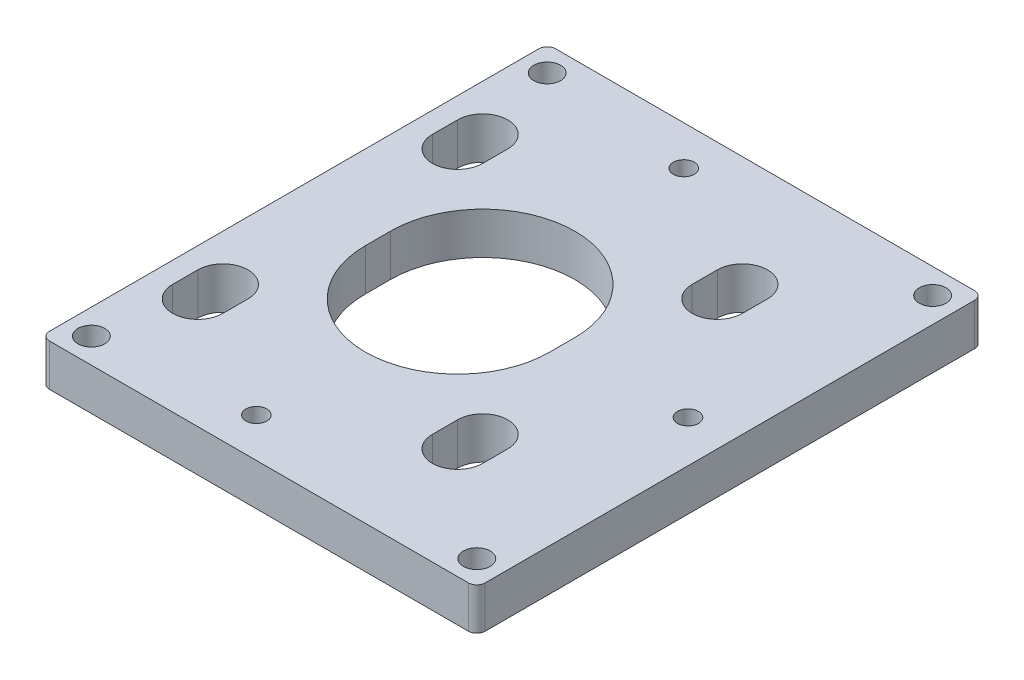
SolidWorks part; units mm, degrees
material "AISI 1045 Steel, cold drawn"
ref_plane "Front Plane" through (0, 0, 0) normal (0, 0, 1) x (1, 0, 0)
ref_plane "Top Plane" through (0, 0, 0) normal (0, 1, 0) x (1, 0, 0)
ref_plane "Right Plane" through (0, 0, 0) normal (1, 0, 0) x (0, 0, -1)
sketch "Sketch1" plane through (0, 0, 0) normal (0, 1, 0) x (1, 0, 0)
  line L0 (0, -1.5) -> (0, 1.5) construction
  line L1 (-11, -1.5) -> (-11, 1.5)
  line L2 (11, -1.5) -> (11, 1.5)
  line L3 (-15.5, 14) -> (-15.5, 17) construction
  line L4 (-18.5, 14) -> (-18.5, 17)
  line L5 (-12.5, 14) -> (-12.5, 17)
  line L6 (15.5, 14) -> (15.5, 17) construction
  line L7 (12.5, 14) -> (12.5, 17)
  line L8 (18.5, 14) -> (18.5, 17)
  line L9 (15.5, -17) -> (15.5, -14) construction
  line L10 (12.5, -17) -> (12.5, -14)
  line L11 (18.5, -17) -> (18.5, -14)
  line L12 (-15.5, -17) -> (-15.5, -14) construction
  line L13 (-18.5, -17) -> (-18.5, -14)
  line L14 (-12.5, -17) -> (-12.5, -14)
  line L15 (-15.5, 15.5) -> (15.5, 15.5) construction
  line L16 (-15.5, -15.5) -> (-15.5, 15.5) construction
  line L17 (21, -30.2) -> (21, 30.2) construction
  line L18 (-21, 30.2) -> (31, 30.2)
  line L19 (-21, 30.2) -> (-21, -30.2)
  line L20 (-21, -30.2) -> (31, -30.2)
  line L21 (31, 30.2) -> (31, -30.2)
  arc A0 (-11, -1.5) -> (11, -1.5) centre (0, -1.5) ccw
  arc A1 (11, 1.5) -> (-11, 1.5) centre (0, 1.5) ccw
  arc A2 (-18.5, 14) -> (-12.5, 14) centre (-15.5, 14) ccw
  arc A3 (-12.5, 17) -> (-18.5, 17) centre (-15.5, 17) ccw
  arc A4 (12.5, 14) -> (18.5, 14) centre (15.5, 14) ccw
  arc A5 (18.5, 17) -> (12.5, 17) centre (15.5, 17) ccw
  arc A6 (12.5, -17) -> (18.5, -17) centre (15.5, -17) ccw
  arc A7 (18.5, -14) -> (12.5, -14) centre (15.5, -14) ccw
  arc A8 (-18.5, -17) -> (-12.5, -17) centre (-15.5, -17) ccw
  arc A9 (-12.5, -14) -> (-18.5, -14) centre (-15.5, -14) ccw
  point P2 (0, 0)
  point P10 (-15.5, 15.5)
  point P16 (15.5, 15.5)
  point P23 (15.5, -15.5)
  point P30 (-15.5, -15.5)
  point P38 (0, 15.5)
  point P40 (-15.5, 0)
  point P43 (31, 0)
  dimension "D2" = 11
  dimension "D3" = 3
  dimension "D1" = 3
  dimension "D4" = 31
  dimension "D5" = 3
  dimension "D6" = 30.2
  dimension "D7" = 21
  dimension "D8" = 21
  dimension "D9" = 10
extrude "Boss-Extrude1" add sketch "Sketch1" along normal blind 5
hole_wizard "M3 Clearance Hole1" positions "Sketch2" profile "Sketch3" hole size "M3" standard "ANSI Metric" end condition through all
sketch "Sketch2" plane through (0, 5, 0) normal (0, 1, 0) x (1, 0, 0)
  line L0 (-21, -30.2) -> (31, -30.2) construction
  line L1 (-21, 30.2) -> (-21, -30.2) construction
  line L2 (31, -30.2) -> (31, 30.2) construction
  line L3 (31, 30.2) -> (-21, 30.2) construction
  point P0 (-18, -27.2)
  point P2 (28, -27.2)
  point P4 (28, 27.2)
  point P6 (-18, 27.2)
  dimension "D1" = 3
  dimension "D2" = 3
  dimension "D3" = 3
  dimension "D4" = 3
sketch "Sketch3" plane through (-18, 5, 27.2) normal (1, 0, 0) x (0, 0, 1)
  line L0 (0, 0) -> (0, 5)
  line L1 (0, 5) -> (1.6, 5)
  line L2 (1.6, 5) -> (1.6, 0)
  line L5 (1.6, 0) -> (0, 0)
  line L11 (0, -6.35) -> (0, 107.95) construction
  dimension "Thru Hole Dia." = 3.2
  dimension "Thru Hole Depth" = 5
fillet "Fillet1" radius 1 4 edges at (31, 2.5, -30.2) (-21, 2.5, -30.2) (31, 2.5, 30.2) (-21, 2.5, 30.2)
hole_wizard "Tap Drill for M3x0.5 Tap1" positions "Sketch4" profile "Sketch5" hole size "M3x0.5" standard "ANSI Metric" end condition through all
sketch "Sketch4" plane through (0, 5, 0) normal (0, 1, 0) x (1, 0, 0)
  point P0 (26, 0)
  point P6 (0, 25.5)
  point P8 (0, -25.5)
  dimension "D1" = 26
  dimension "D2" = 25.5
  dimension "D3" = 25.5
sketch "Sketch5" plane through (26, 5, 0) normal (1, 0, 0) x (0, 0, 1)
  line L0 (0, 0) -> (0, 5)
  line L1 (0, 5) -> (1.25, 5)
  line L2 (1.25, 5) -> (1.25, 0)
  line L5 (1.25, 0) -> (0, 0)
  line L11 (0, -6.35) -> (0, 107.95) construction
  dimension "Thru Hole Dia." = 2.5
  dimension "Thru Hole Depth" = 5
